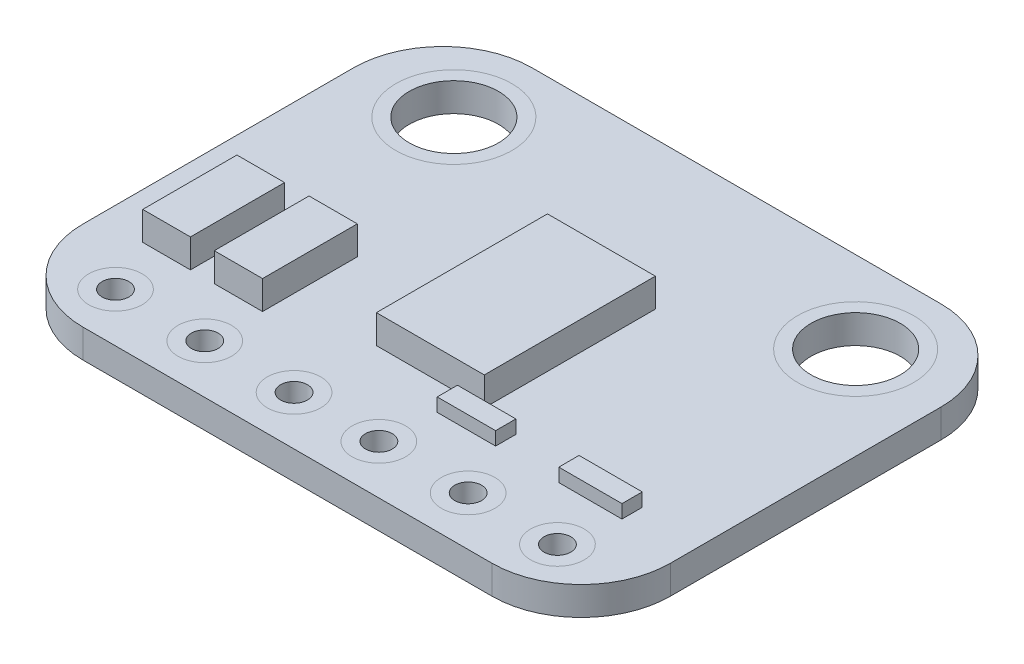
SolidWorks part; units mm, degrees
ref_plane "Front Plane" through (0, 0, 0) normal (0, 0, 1) x (1, 0, 0)
ref_plane "Top Plane" through (0, 0, 0) normal (0, 1, 0) x (1, 0, 0)
ref_plane "Right Plane" through (0, 0, 0) normal (1, 0, 0) x (0, 0, -1)
sketch "Sketch1" plane through (0, 0, 0) normal (0, 1, 0) x (1, 0, 0)
  line L1 (5.8166, 6.3881) -> (-5.8166, 6.3881)
  line L2 (8.3566, 3.8481) -> (8.3566, -3.8481)
  line L3 (5.8166, -6.3881) -> (-5.8166, -6.3881)
  line L4 (-8.3566, 3.8481) -> (-8.3566, -3.8481)
  line L5 (8.3566, 6.3881) -> (-8.3566, -6.3881) construction
  line L6 (8.3566, -6.3881) -> (-8.3566, 6.3881) construction
  arc A0 (8.3566, -3.8481) -> (5.8166, -6.3881) centre (5.8166, -3.8481) cw
  arc A1 (5.8166, 6.3881) -> (8.3566, 3.8481) centre (5.8166, 3.8481) cw
  arc A2 (-5.8166, 6.3881) -> (-8.3566, 3.8481) centre (-5.8166, 3.8481) ccw
  arc A3 (-5.8166, -6.3881) -> (-8.3566, -3.8481) centre (-5.8166, -3.8481) cw
  point P0 (0, 0)
  dimension "D3" = 2.54
  dimension "D1" = 16.7132
  dimension "D2" = 12.7762
extrude "Boss-Extrude1" add sketch "Sketch1" along normal blind 0.8128
sketch "Sketch2" plane through (0, 0.8128, 0) normal (0, 1, 0) x (1, 0, 0)
  line L0 (0, 6.3881) -> (0, -6.3881) construction
  line L1 (5.8166, 6.3881) -> (-5.8166, 6.3881) construction
  line L2 (-5.8166, -6.3881) -> (5.8166, -6.3881) construction
  line L3 (-4.445, 4.0611) -> (4.445, 4.0611) construction
  line L4 (-0.8255, -4.9937) -> (0.8255, -4.9937) construction
  circle A0 centre (-1.2065, -4.9937) radius 0.381
  circle A1 centre (-5.715, 4.0611) radius 1.27
  circle A2 centre (-3.7465, -4.9937) radius 0.381
  circle A3 centre (-6.2865, -4.9937) radius 0.381
  circle A4 centre (6.2865, -4.9937) radius 0.381
  circle A5 centre (3.7465, -4.9937) radius 0.381
  circle A6 centre (5.715, 4.0611) radius 1.27
  circle A7 centre (1.2065, -4.9937) radius 0.381
  point P19 (0, -4.9937)
  point P20 (0, 4.0611)
  dimension "D3" = 2.54
  dimension "D4" = 0.762
  dimension "D1" = 4.445
  dimension "D2" = 0.8255
  dimension "D5" = 3
extrude "Cut-Extrude1" cut sketch "Sketch2" against normal blind 0.8128
sketch "Sketch3" plane through (0, 0.8128, 0) normal (0, 1, 0) x (1, 0, 0)
  circle A0 centre (-5.715, 4.0611) radius 1.651
  circle A1 centre (-5.715, 4.0611) radius 1.27
  circle A2 centre (-5.715, 4.0611) radius 1.27 construction
  circle A3 centre (-1.2065, -4.9937) radius 0.381
  circle A4 centre (-1.2065, -4.9937) radius 0.381 construction
  circle A5 centre (1.2065, -4.9937) radius 0.381
  circle A6 centre (1.2065, -4.9937) radius 0.381 construction
  circle A7 centre (5.715, 4.0611) radius 1.27
  circle A8 centre (5.715, 4.0611) radius 1.27 construction
  circle A9 centre (3.7465, -4.9937) radius 0.381
  circle A10 centre (3.7465, -4.9937) radius 0.381 construction
  circle A11 centre (6.2865, -4.9937) radius 0.381
  circle A12 centre (6.2865, -4.9937) radius 0.381 construction
  circle A13 centre (-6.2865, -4.9937) radius 0.381
  circle A14 centre (-6.2865, -4.9937) radius 0.381 construction
  circle A15 centre (-3.7465, -4.9937) radius 0.381
  circle A16 centre (-3.7465, -4.9937) radius 0.381 construction
  circle A17 centre (-1.2065, -4.9937) radius 0.762
  circle A18 centre (1.2065, -4.9937) radius 0.762
  circle A19 centre (5.715, 4.0611) radius 1.651
  circle A20 centre (3.7465, -4.9937) radius 0.762
  circle A21 centre (6.2865, -4.9937) radius 0.762
  circle A22 centre (-6.2865, -4.9937) radius 0.762
  circle A23 centre (-3.7465, -4.9937) radius 0.762
  dimension "D1" = 0
  dimension "D2" = 0
  dimension "D3" = 0
  dimension "D4" = 0
  dimension "D5" = 0
  dimension "D6" = 0
  dimension "D7" = 0
  dimension "D8" = 0
  dimension "D9" = 0.381
split line "Split Line1"
sketch "Sketch4" plane through (0, 0.8128, 0) normal (0, 1, 0) x (1, 0, 0)
  line L1 (-1.187, 2.1959) -> (1.8822, 2.1959)
  line L2 (-1.187, 2.1959) -> (-1.187, -2.6707)
  line L3 (-1.187, -2.6707) -> (1.8822, -2.6707)
  line L4 (1.8822, 2.1959) -> (1.8822, -2.6707)
  line L5 (1.3226, -2.8741) -> (2.9843, -2.8741)
  line L6 (1.3226, -2.8741) -> (1.3226, -3.4507)
  line L7 (1.3226, -3.4507) -> (2.9843, -3.4507)
  line L8 (2.9843, -2.8741) -> (2.9843, -3.4507)
  line L9 (4.7817, -2.8741) -> (6.5791, -2.8741)
  line L10 (4.7817, -2.8741) -> (4.7817, -3.4507)
  line L11 (4.7817, -3.4507) -> (6.5791, -3.4507)
  line L12 (6.5791, -2.8741) -> (6.5791, -3.4507)
  line L13 (-7.0539, -3.4507) -> (-5.6974, -3.4507)
  line L14 (-7.0539, -3.4507) -> (-7.0539, -0.7715)
  line L15 (-7.0539, -0.7715) -> (-5.6974, -0.7715)
  line L16 (-5.6974, -3.4507) -> (-5.6974, -0.7715)
  line L17 (-5.0191, -3.4507) -> (-3.6457, -3.4507)
  line L18 (-5.0191, -3.4507) -> (-5.0191, -0.7546)
  line L19 (-5.0191, -0.7546) -> (-3.6457, -0.7546)
  line L20 (-3.6457, -3.4507) -> (-3.6457, -0.7546)
extrude "Boss-Extrude2" add sketch "Sketch4" along normal blind 0.8128 contours L4 L1 L2 L3 | L17 L20 L19 L18 | L13 L16 L15 L14 region at (0.3476, 0.8128, 0.2374)
extrude "Boss-Extrude3" add sketch "Sketch4<3>" along normal blind 0.381 contours L7 L8 L5 L6 | L11 L12 L9 L10
sketch "Sketch4<3>" plane through (0, 0.8128, 0) normal (0, 1, 0) x (1, 0, 0) same geometry as "Sketch4"
